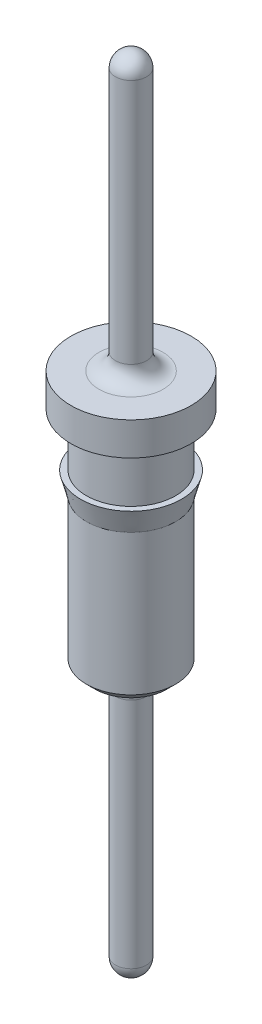
SolidWorks part; units mm, degrees
ref_plane "Front Plane" through (0, 0, 0) normal (0, 0, 1) x (1, 0, 0)
ref_plane "Top Plane" through (0, 0, 0) normal (0, 1, 0) x (1, 0, 0)
ref_plane "Right Plane" through (0, 0, 0) normal (1, 0, 0) x (0, 0, -1)
sketch "Sketch1" plane through (0, 0, 0) normal (0, 0, 1) x (1, 0, 0)
  line L0 (0, 0) -> (0, 11.64)
  line L1 (0, 11.64) -> (0.235, 11.64)
  line L2 (0.235, 11.64) -> (0.235, 7.67)
  line L3 (0.235, 7.67) -> (0.91, 7.67)
  line L4 (0.91, 7.67) -> (0.91, 7.17)
  line L5 (0.91, 7.17) -> (0.675, 7.17)
  line L6 (0.675, 7.17) -> (0.675, 6.37)
  line L7 (0.675, 6.37) -> (0.765, 6.37)
  line L8 (0.765, 6.37) -> (0.675, 6.03)
  line L9 (0.675, 6.03) -> (0.675, 3.9)
  line L10 (0.675, 3.9) -> (0.545, 3.77)
  line L11 (0.545, 3.77) -> (0.235, 3.77)
  line L12 (0.235, 3.77) -> (0.235, 0)
  line L13 (0.235, 0) -> (0, 0)
  dimension "D1" = 0.235
  dimension "D2" = 0.675
  dimension "D3" = 0.765
  dimension "D4" = 0.91
  dimension "D5" = 3.77
  dimension "D6" = 0.13
  dimension "D7" = 2.13
  dimension "D8" = 0.34
  dimension "D9" = 0.8
  dimension "D10" = 0.5
  dimension "D11" = 3.97
  dimension "D12" = 0.13
revolve "Revolve1" add sketch "Sketch1" angle 360 about L0
dome "Dome1" faces to dome 1 distance 0.235 reverse direction no elliptical dome no face at (0, 11.64, -0.235) parameters "D1"=0.235
dome "Dome2" faces to dome 1 distance 0.235 reverse direction no elliptical dome no face at (0, 0, -0.235) parameters "D1"=0.235
fillet "Fillet1" radius 0.25 2 edges at (0, 3.77, -0.235) (0, 7.67, -0.235)
